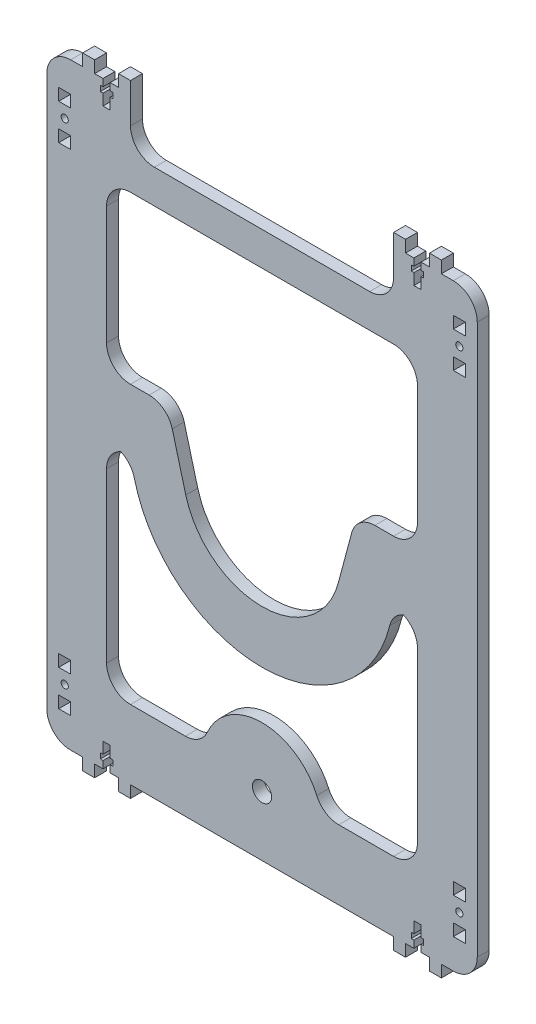
SolidWorks part; units mm, degrees
ref_plane "Front Plane" through (0, 0, 0) normal (0, 0, 1) x (1, 0, 0)
ref_plane "Top Plane" through (0, 0, 0) normal (0, 1, 0) x (1, 0, 0)
ref_plane "Right Plane" through (0, 0, 0) normal (1, 0, 0) x (0, 0, -1)
sketch "Sketch1" plane through (0, 0, 0) normal (0, 0, 1) x (1, 0, 0)
  line L0 (0, 0) -> (187.0096, 0) construction
  line L1 (-90, 125) -> (-55, 125) construction
  line L2 (-90, 125) -> (-90, -125)
  line L3 (-90, -125) -> (90, -125)
  line L4 (90, 125) -> (90, -125)
  line L5 (0, 0) -> (0, 134.5508) construction
  line L6 (-31.8756, -8.541) -> (-39.5231, 20)
  line L7 (-65, 89.5396) -> (65, 89.5396)
  line L8 (65, 89.5396) -> (65, 0) construction
  line L9 (65, 0) -> (-65, 0) construction
  line L10 (-65, 0) -> (-65, 89.5396) construction
  line L11 (-65, 0) -> (-20, 0) construction
  line L12 (20, 0) -> (65, 0) construction
  line L13 (82.5, 125) -> (82.5, -125) construction
  line L14 (0, 0) -> (0, -125) construction
  line L21 (-39.5231, 20) -> (-65, 20)
  line L22 (-65, 20) -> (-65, 89.5396)
  line L23 (65, 20) -> (65, 89.5396)
  line L24 (39.5231, 20) -> (65, 20)
  line L26 (-90, 125) -> (-55, 125)
  line L27 (31.8756, -8.541) -> (39.5231, 20)
  line L28 (-55, 125) -> (-55, 103.5988)
  line L29 (-55, 103.5988) -> (55, 103.5988)
  line L30 (55, 103.5988) -> (55, 125)
  line L31 (55, 125) -> (90, 125) construction
  line L32 (55, 125) -> (90, 125)
  line L33 (-54.7172, -5.5707) -> (-65, -5.5707)
  line L34 (-65, -5.5707) -> (-65, -95.958)
  line L35 (-65, -95.958) -> (-24.6711, -95.958)
  line L36 (54.7172, -5.5707) -> (65, -5.5707)
  line L37 (65, -5.5707) -> (65, -95.958)
  line L38 (65, -95.958) -> (24.6711, -95.958)
  circle A1 centre (0, -100) radius 4
  circle A2 centre (0, 0) radius 33 construction
  arc A3 (31.8756, -8.541) -> (-31.8756, -8.541) centre (0, 0) cw
  circle A4 centre (0, 0) radius 55 construction
  circle A5 centre (0, -100) radius 25 construction
  arc A6 (24.6711, -95.958) -> (-24.6711, -95.958) centre (0, -100) ccw
  arc A7 (-54.7172, -5.5707) -> (54.7172, -5.5707) centre (0, 0) ccw
  line B0 (82.5, 107.5) -> (82.5, 97.5) construction
  line B1 (80, 107.5) -> (80, 112.5)
  line B2 (80, 107.5) -> (85, 107.5)
  line B3 (85, 107.5) -> (85, 112.5)
  line B4 (80, 112.5) -> (85, 112.5)
  line B5 (80, 97.5) -> (80, 92.5)
  line B6 (80, 97.5) -> (85, 97.5)
  line B7 (85, 97.5) -> (85, 92.5)
  line B8 (80, 92.5) -> (85, 92.5)
  line B9 (82.5, 102.5) -> (75.5276, 102.5) construction
  circle B10 centre (82.5, 102.5) radius 1.5
  line B11 (82.5, -107.5) -> (82.5, -97.5) construction
  line B12 (80, -107.5) -> (80, -112.5)
  line B13 (80, -107.5) -> (85, -107.5)
  line B14 (85, -107.5) -> (85, -112.5)
  line B15 (80, -112.5) -> (85, -112.5)
  line B16 (80, -97.5) -> (80, -92.5)
  line B17 (80, -97.5) -> (85, -97.5)
  line B18 (85, -97.5) -> (85, -92.5)
  line B19 (80, -92.5) -> (85, -92.5)
  line B20 (82.5, -102.5) -> (75.5276, -102.5) construction
  circle B21 centre (82.5, -102.5) radius 1.5
  line B22 (-82.5, 107.5) -> (-82.5, 97.5) construction
  line B23 (-80, 107.5) -> (-80, 112.5)
  line B24 (-80, 107.5) -> (-85, 107.5)
  line B25 (-85, 107.5) -> (-85, 112.5)
  line B26 (-80, 112.5) -> (-85, 112.5)
  line B27 (-80, 97.5) -> (-80, 92.5)
  line B28 (-80, 97.5) -> (-85, 97.5)
  line B29 (-85, 97.5) -> (-85, 92.5)
  line B30 (-80, 92.5) -> (-85, 92.5)
  line B31 (-82.5, 102.5) -> (-75.5276, 102.5) construction
  circle B32 centre (-82.5, 102.5) radius 1.5
  line B33 (-82.5, -107.5) -> (-82.5, -97.5) construction
  line B34 (-80, -107.5) -> (-80, -112.5)
  line B35 (-80, -107.5) -> (-85, -107.5)
  line B36 (-85, -107.5) -> (-85, -112.5)
  line B37 (-80, -112.5) -> (-85, -112.5)
  line B38 (-80, -97.5) -> (-80, -92.5)
  line B39 (-80, -97.5) -> (-85, -97.5)
  line B40 (-85, -97.5) -> (-85, -92.5)
  line B41 (-80, -92.5) -> (-85, -92.5)
  line B42 (-82.5, -102.5) -> (-75.5276, -102.5) construction
  circle B43 centre (-82.5, -102.5) radius 1.5
  line B44 (-67.6, -122) -> (-67.6, -119.7)
  line B45 (-63.5, -119.7) -> (-63.5, -115)
  line B46 (-66.5, -115) -> (-66.5, -119.7)
  line B47 (-67.6, -119.7) -> (-66.5, -119.7)
  line B48 (-65, -125) -> (-65, -113.7792) construction
  line B49 (-66.5, -125) -> (-70, -125)
  line B50 (-70, -130) -> (-75, -130)
  line B51 (-75, -130) -> (-75, -125)
  line B52 (-70, -130) -> (-70, -125)
  line B53 (-63.5, -125) -> (-60, -125)
  line B54 (-60, -125) -> (-60, -130)
  line B55 (-60, -130) -> (-55, -130)
  line B56 (-55, -130) -> (-55, -125)
  line B57 (-66.5, -125) -> (-63.5, -125) construction
  line B58 (-63.5, -125) -> (-63.5, -122)
  line B59 (-63.5, -119.7) -> (-62.4, -119.7)
  line B60 (-62.4, -122) -> (-63.5, -122)
  line B61 (-63.5, -115) -> (-66.5, -115)
  line B62 (-66.5, -122) -> (-67.6, -122)
  line B63 (-62.4, -119.7) -> (-62.4, -122)
  line B64 (-66.5, -122) -> (-66.5, -125)
  line B65 (-65, -115) -> (-65, -125) construction
  line B66 (62.4, -122) -> (62.4, -119.7)
  line B67 (66.5, -119.7) -> (66.5, -115)
  line B68 (63.5, -115) -> (63.5, -119.7)
  line B69 (62.4, -119.7) -> (63.5, -119.7)
  line B70 (65, -125) -> (65, -113.7792) construction
  line B71 (63.5, -125) -> (60, -125)
  line B72 (60, -130) -> (55, -130)
  line B73 (55, -130) -> (55, -125)
  line B74 (60, -130) -> (60, -125)
  line B75 (66.5, -125) -> (70, -125)
  line B76 (70, -125) -> (70, -130)
  line B77 (70, -130) -> (75, -130)
  line B78 (75, -130) -> (75, -125)
  line B79 (63.5, -125) -> (66.5, -125) construction
  line B80 (66.5, -125) -> (66.5, -122)
  line B81 (66.5, -119.7) -> (67.6, -119.7)
  line B82 (67.6, -122) -> (66.5, -122)
  line B83 (66.5, -115) -> (63.5, -115)
  line B84 (63.5, -122) -> (62.4, -122)
  line B85 (67.6, -119.7) -> (67.6, -122)
  line B86 (63.5, -122) -> (63.5, -125)
  line B87 (65, -115) -> (65, -125) construction
  line B88 (67.6, 122) -> (67.6, 119.7)
  line B89 (63.5, 119.7) -> (63.5, 115)
  line B90 (66.5, 115) -> (66.5, 119.7)
  line B91 (67.6, 119.7) -> (66.5, 119.7)
  line B92 (65, 125) -> (65, 113.7792) construction
  line B93 (66.5, 125) -> (70, 125)
  line B94 (70, 130) -> (75, 130)
  line B95 (75, 130) -> (75, 125)
  line B96 (70, 130) -> (70, 125)
  line B97 (63.5, 125) -> (60, 125)
  line B98 (60, 125) -> (60, 130)
  line B99 (60, 130) -> (55, 130)
  line B100 (55, 130) -> (55, 125)
  line B101 (66.5, 125) -> (63.5, 125) construction
  line B102 (63.5, 125) -> (63.5, 122)
  line B103 (63.5, 119.7) -> (62.4, 119.7)
  line B104 (62.4, 122) -> (63.5, 122)
  line B105 (63.5, 115) -> (66.5, 115)
  line B106 (66.5, 122) -> (67.6, 122)
  line B107 (62.4, 119.7) -> (62.4, 122)
  line B108 (66.5, 122) -> (66.5, 125)
  line B109 (65, 115) -> (65, 125) construction
  line B110 (-62.4, 122) -> (-62.4, 119.7)
  line B111 (-66.5, 119.7) -> (-66.5, 115)
  line B112 (-63.5, 115) -> (-63.5, 119.7)
  line B113 (-62.4, 119.7) -> (-63.5, 119.7)
  line B114 (-65, 125) -> (-65, 113.7792) construction
  line B115 (-63.5, 125) -> (-60, 125)
  line B116 (-60, 130) -> (-55, 130)
  line B117 (-55, 130) -> (-55, 125)
  line B118 (-60, 130) -> (-60, 125)
  line B119 (-66.5, 125) -> (-70, 125)
  line B120 (-70, 125) -> (-70, 130)
  line B121 (-70, 130) -> (-75, 130)
  line B122 (-75, 130) -> (-75, 125)
  line B123 (-63.5, 125) -> (-66.5, 125) construction
  line B124 (-66.5, 125) -> (-66.5, 122)
  line B125 (-66.5, 119.7) -> (-67.6, 119.7)
  line B126 (-67.6, 122) -> (-66.5, 122)
  line B127 (-66.5, 115) -> (-63.5, 115)
  line B128 (-63.5, 122) -> (-62.4, 122)
  line B129 (-67.6, 119.7) -> (-67.6, 122)
  line B130 (-63.5, 122) -> (-63.5, 125)
  line B131 (-65, 115) -> (-65, 125) construction
  dimension "D8" = 50
  dimension "D10" = 8
  dimension "D2" = 33
  dimension "D13" = 110
  dimension "D3" = 250
  dimension "D4" = 180
  dimension "D5" = 105
  dimension "D6" = 25
  dimension "D7" = 20
  dimension "D9" = 22.5
  dimension "D11" = 25
  dimension "D12" = 7.5
sketch_block_instance "Trou M3 plots 5mm-7"
sketch_block "Trou M3 plots 5mm" parameters "D2"=3, "D1"=5, "D3"=5, "D4"=10
sketch_block_instance "Trou M3 plots 5mm-8"
sketch_block_instance "Trou M3 plots 5mm-9"
sketch_block_instance "Trou M3 plots 5mm-10"
sketch_block_instance "Insert M3 plots ep 5mm-1"
sketch_block "Insert M3 plots ep 5mm" parameters "D1"=10, "D2"=5, "D3"=5
sketch_block_instance "Decoupe Insert M3-4"
sketch_block "Decoupe Insert M3" parameters "D1"=5.2, "D2"=3, "D3"=2.3, "D4"=3, "D5"=10
sketch_block_instance "Insert M3 plots ep 5mm-2"
sketch_block_instance "Insert M3 plots ep 5mm-3"
sketch_block_instance "Insert M3 plots ep 5mm-5"
extrude "Boss-Extrude1" add sketch "Sketch1" along normal blind 5 contours B130 B128 B110 B113 B112 B127 B111 B125 B129 B126 B124 L26 L2 L3 B64 B62 B44 B47 B46 B61 B45 B59 B63 B60 B58 B86 B84 B66 B69 B68 B83 B67 B81 B85 B82 B80 L4 | B50 B52 L3 B51 | B55 B56 L3 B54 | B72 B74 L3 B73 | B77 B78 L3 B76 | B121 B122 L26 B120 | B116 B118 L26 B117 | B99 B100 L26 B98 | B94 B96 L26 B95 region at (-82.5, 121.9194, 0) region at (-72.5, 127.5, 0) region at (-72.5, -127.5, 0) region at (-57.5, 127.5, 0) region at (-57.5, -127.5, 0) region at (57.5, -127.5, 0) region at (57.5, 127.5, 0) region at (72.5, -127.5, 0) region at (72.5, 127.5, 0)
fillet "Fillet1" radius 10 20 edges at (-90, -125, 2.5) (90, -125, 2.5) (-90, 125, 2.5) (90, 125, 2.5) (-55, 103.5988, 2.5) (55, 103.5988, 2.5) (24.6711, -95.958, 2.5) (-24.6711, -95.958, 2.5) (-65, -95.958, 2.5) (65, -95.958, 2.5) (65, -5.5707, 2.5) (54.7172, -5.5707, 2.5) (-54.7172, -5.5707, 2.5) (-65, -5.5707, 2.5) (65, 89.5396, 2.5) (-65, 89.5396, 2.5) (65, 20, 2.5) (-65, 20, 2.5) (39.5231, 20, 2.5) (-39.5231, 20, 2.5)
